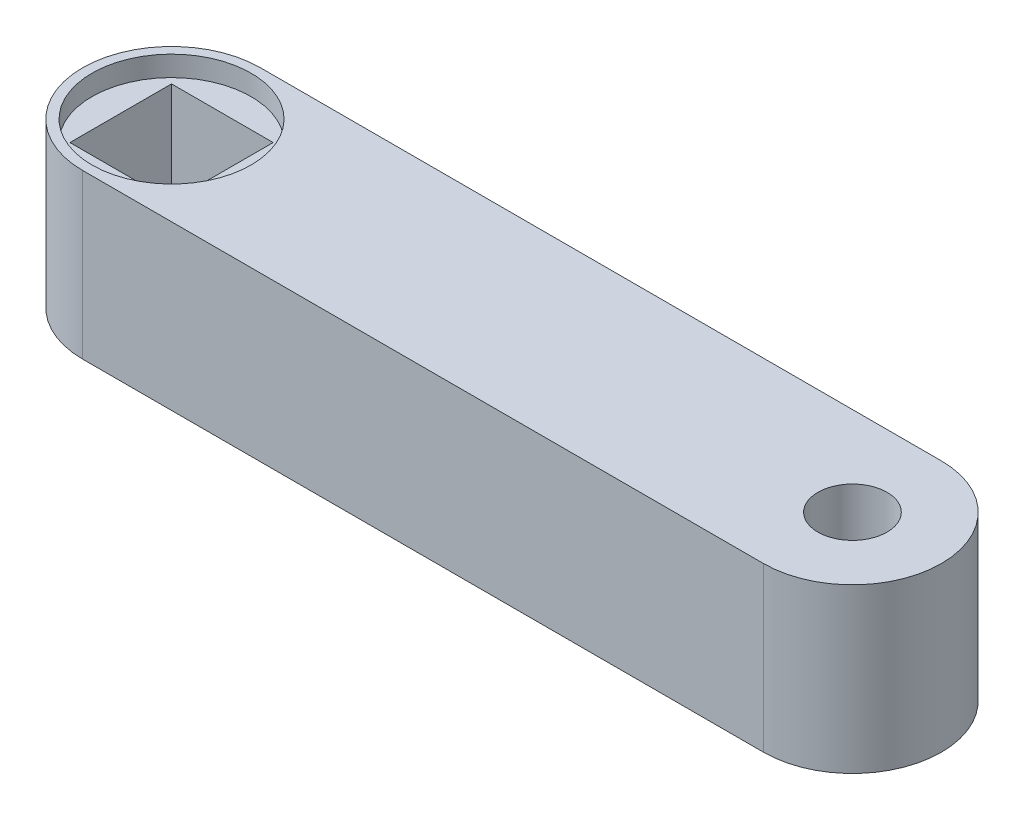
SolidWorks part; units mm, degrees
ref_plane "Front Plane" through (0, 0, 0) normal (0, 0, 1) x (1, 0, 0)
ref_plane "Top Plane" through (0, 0, 0) normal (0, 1, 0) x (1, 0, 0)
ref_plane "Right Plane" through (0, 0, 0) normal (1, 0, 0) x (0, 0, -1)
sketch "Sketch1" plane through (0, 0, 0) normal (0, 1, 0) x (1, 0, 0)
  line L0 (0, 0) -> (42.545, 0) construction
  line L1 (0, 5.5563) -> (42.545, 5.5563)
  line L2 (0, -5.5563) -> (42.545, -5.5563)
  arc A1 (0, 5.5563) -> (0, -5.5563) centre (0, 0) ccw
  arc A2 (42.545, -5.5563) -> (42.545, 5.5563) centre (42.545, 0) ccw
  point P3 (21.2725, 0)
  dimension "D1" = 11.1125
  dimension "D2" = 42.545
extrude "Boss-Extrude1" add sketch "Sketch1" along normal blind 10.2108
sketch "Sketch2" plane through (0, 10.2108, 0) normal (0, 1, 0) x (1, 0, 0)
  line L1 (-3.175, 3.175) -> (3.175, 3.175)
  line L2 (-3.175, 3.175) -> (-3.175, -3.175)
  line L3 (-3.175, -3.175) -> (3.175, -3.175)
  line L4 (3.175, 3.175) -> (3.175, -3.175)
  line L5 (-3.175, 3.175) -> (3.175, -3.175) construction
  line L6 (-3.175, -3.175) -> (3.175, 3.175) construction
  circle A1 centre (42.545, 0) radius 2.159
  point P0 (0, 0)
  dimension "D2" = 6.35
  dimension "D3" = 4.318
  dimension "D1" = 6.35
  dimension "D4" = 42.545
extrude "Cut-Extrude1" cut sketch "Sketch2" against normal through all
sketch "Sketch3" plane through (0, 10.2108, 0) normal (0, 1, 0) x (1, 0, 0)
  circle A0 centre (0, 0) radius 4.9721
  dimension "D1" = 9.9441
extrude "Cut-Extrude2" cut sketch "Sketch3" against normal blind 1.27
ref_plane "Plane1" through (0, 5.1054, 0) normal (0, 1, 0) x (1, 0, 0)
mirror "Mirror1" about plane through (0, 5.1054, 0) normal (0, 1, 0) of "Cut-Extrude2"
